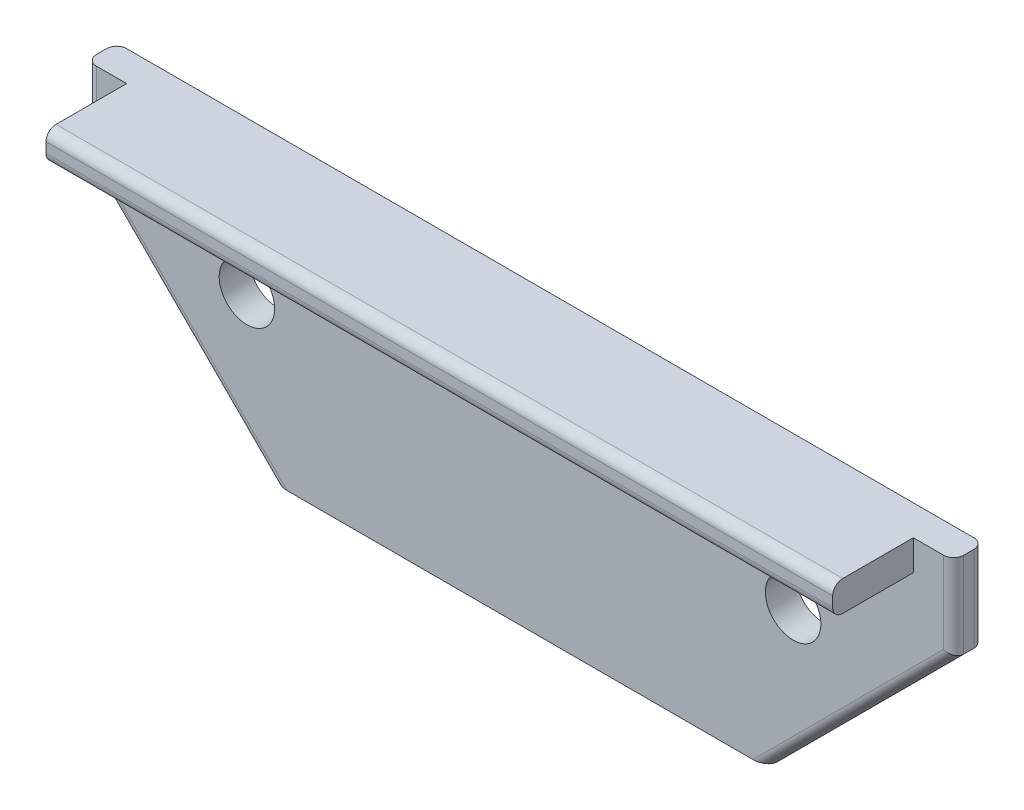
SolidWorks part; units mm, degrees
material "6061 Alloy"
ref_plane "Front Plane" through (0, 0, 0) normal (0, 0, 1) x (1, 0, 0)
ref_plane "Top Plane" through (0, 0, 0) normal (0, 1, 0) x (1, 0, 0)
ref_plane "Right Plane" through (0, 0, 0) normal (1, 0, 0) x (0, 0, -1)
ref_plane "Plane1" through (0, 0, -7.9375) normal (0, 0, 1) x (1, 0, 0)
sketch "Sketch1" plane through (0, 0, -7.9375) normal (0, 0, 1) x (1, 0, 0)
  line L0 (136.525, 15.875) -> (136.525, 42.8625)
  line L1 (136.525, 42.8625) -> (-136.525, 42.8625)
  line L2 (-136.525, 42.8625) -> (-136.525, 15.875)
  line L3 (-136.525, 15.875) -> (-77.7875, -42.8625)
  line L4 (-77.7875, -42.8625) -> (77.7875, -42.8625)
  line L5 (77.7875, -42.8625) -> (136.525, 15.875)
extrude "Boss-Extrude1" add sketch "Sketch1" against normal blind 9.525
sketch "Sketch2" plane through (0, 0, -7.9375) normal (0, 0, 1) x (1, 0, 0)
  line L0 (-123.825, 33.3375) -> (-123.825, 42.8625)
  line L1 (-123.825, 42.8625) -> (123.825, 42.8625)
  line L2 (123.825, 42.8625) -> (123.825, 33.3375)
  line L3 (123.825, 33.3375) -> (-123.825, 33.3375)
extrude "Boss-Extrude2" add sketch "Sketch2" along normal blind 25.4
hole_wizard "M16 Clearance Hole1" positions "Sketch4" profile "Sketch3" hole size "M16" standard "ANSI Metric"
sketch "Sketch4" plane through (0, 0, -17.4625) normal (0, 0, -1) x (-1, 0, 0)
  point P0 (-85.979, 4.7625)
  point P1 (85.979, 4.7625)
sketch "Sketch3" plane through (85.979, 4.7625, -17.4625) normal (1, 0, 0) x (0, 1, 0)
  line L0 (0, 0) -> (0, 34.925)
  line L1 (0, 34.925) -> (8.7312, 34.925)
  line L2 (8.7312, 34.925) -> (8.7312, 0)
  line L5 (8.7312, 0) -> (0, 0)
  line L11 (0, -6.35) -> (0, 107.95) construction
  dimension "Thru Hole Dia." = 17.4625
  dimension "Thru Hole Depth" = 34.925
fillet "Fillet1" radius 3.175 10 edges at (-107.1562, -13.4937, -17.4625) (-136.525, 29.3687, -17.4625) (-136.525, 29.3687, -7.9375) (-107.1562, -13.4937, -7.9375) (136.525, 29.3687, -17.4625) (107.1562, -13.4937, -17.4625) (0, 42.8625, 17.4625) (107.1562, -13.4937, -7.9375) (136.525, 29.3687, -7.9375) (0, 33.3375, 17.4625) tangent propagation no
